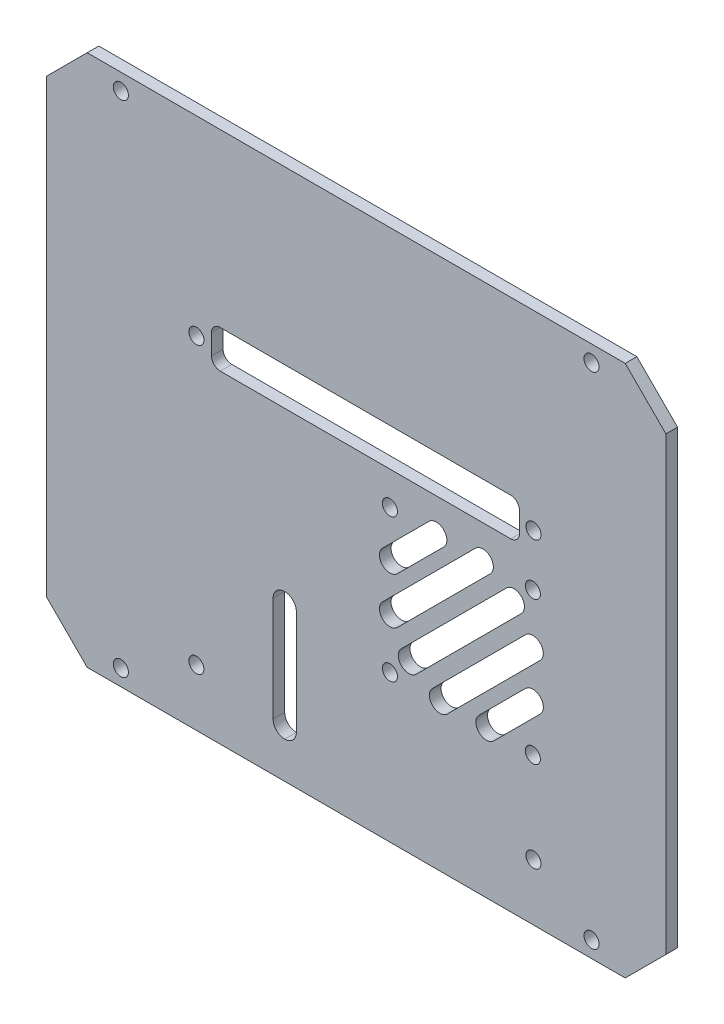
SolidWorks part; units mm, degrees
ref_plane "前视基准面" through (0, 0, 0) normal (0, 0, 1) x (1, 0, 0)
ref_plane "上视基准面" through (0, 0, 0) normal (0, 1, 0) x (1, 0, 0)
ref_plane "右视基准面" through (0, 0, 0) normal (1, 0, 0) x (0, 0, -1)
sketch "草图2" plane through (0, 0, -42.2) normal (0, 0, -1) x (-1, 0, 0)
  line L32 (-57.3467, -34.0538) -> (-50.3426, -41.058)
  line L33 (-50.3426, -41.058) -> (42.2491, -41.058)
  line L34 (42.2491, -41.058) -> (49.2533, -34.0538)
  line L35 (49.2533, -34.0538) -> (49.2533, 43.5378)
  line L36 (49.2533, 43.5378) -> (42.2491, 50.542)
  line L37 (-57.3467, 43.5378) -> (-57.3467, -34.0538)
  line L38 (-50.3426, 50.542) -> (-57.3467, 43.5378)
  line L39 (42.2491, 50.542) -> (-50.3426, 50.542)
  line L40 (-57.3467, -34.0538) -> (-50.3426, -41.058)
  line L41 (-50.3426, -41.058) -> (42.2491, -41.058)
  line L42 (42.2491, -41.058) -> (49.2533, -34.0538)
  line L43 (49.2533, -34.0538) -> (49.2533, 43.5378)
  line L44 (49.2533, 43.5378) -> (42.2491, 50.542)
  line L45 (-57.3467, 43.5378) -> (-57.3467, -34.0538)
  line L46 (-50.3426, 50.542) -> (-57.3467, 43.5378)
  line L47 (42.2491, 50.542) -> (-50.3426, 50.542)
  dimension "D1" = 0.2
extrude "凸台-拉伸1" add sketch "草图2" along normal blind 2
sketch "草图3" plane through (0, 0, -44.2) normal (0, 0, -1) x (-1, 0, 0)
  circle A0 centre (-44.5467, -38.258) radius 1.3
  circle A1 centre (36.4533, -38.258) radius 1.3
  circle A2 centre (-44.5467, 47.742) radius 1.3
  circle A3 centre (36.4533, 47.742) radius 1.3
  dimension "D1" = 2.6
extrude "切除-拉伸1" cut sketch "草图3" against normal through all
sketch "草图4" plane through (0, 0, -44.2) normal (0, 0, -1) x (-1, 0, 0)
  circle A1 centre (23.4533, -31.2932) radius 1.3
  circle A2 centre (23.4533, -31.2932) radius 1.3
  circle A3 centre (-34.5583, -31.2932) radius 1.3
  circle A4 centre (-34.5583, -31.2932) radius 1.3
  circle A5 centre (23.4533, 17.742) radius 1.3
  circle A6 centre (23.4533, 17.742) radius 1.3
  circle A7 centre (-34.5583, 17.742) radius 1.3
  circle A8 centre (-34.5583, 17.742) radius 1.3
  dimension "D1" = 0
  dimension "D2" = 0
  dimension "D3" = 0
  dimension "D4" = 0
extrude "切除-拉伸2" cut sketch "草图4" against normal up to next
sketch "草图5" plane through (0, 0, -44.2) normal (0, 0, -1) x (-1, 0, 0)
  line L0 (-50.4254, -41.258) -> (42.3319, -41.258) construction
  line L1 (-32.1467, 14.542) -> (20.8533, 14.542)
  line L2 (-32.1467, 14.542) -> (-32.1467, 21.042)
  line L3 (-32.1467, 21.042) -> (20.8533, 21.042)
  line L4 (20.8533, 14.542) -> (20.8533, 21.042)
  line L7 (-57.3467, 43.5378) -> (-57.3467, -34.0538) construction
  dimension "D1" = 53
  dimension "D2" = 6.5
  dimension "D3" = 25.2
  dimension "D4" = 55.8
extrude "切除-拉伸3" cut sketch "草图5" against normal up to next
fillet "圆角1" radius 1.5 4 edges at (32.1467, 21.042, -43.2) (32.1467, 14.542, -43.2) (-20.8533, 14.542, -43.2) (-20.8533, 21.042, -43.2)
sketch "草图7" plane through (0, 0, -44.2) normal (0, 0, -1) x (-1, 0, 0)
  line L0 (-59.0467, 44.242) -> (-59.0467, -34.758) construction
  line L1 (42.9533, 52.242) -> (-51.0467, 52.242) construction
  circle A0 centre (-34.4467, 8.842) radius 1.3
  circle A1 centre (-34.4467, -15.758) radius 1.3
  circle A2 centre (-9.8467, 8.842) radius 1.3
  circle A3 centre (-9.8467, -15.758) radius 1.3
  dimension "D1" = 24.6
  dimension "D2" = 24.6
  dimension "D3" = 24.6
  dimension "D4" = 43.4
extrude "切除-拉伸4" cut sketch "草图7" against normal up to next
sketch "草图8" plane through (0, 0, -44.2) normal (0, 0, -1) x (-1, 0, 0)
  line L0 (-34.4467, 8.842) -> (-9.8467, -15.758) construction
  line L1 (-34.4467, 8.842) -> (-9.8467, 8.842) construction
  line L2 (-34.4467, 8.842) -> (-34.4467, -15.758) construction
  line L3 (-34.4467, -15.758) -> (-9.8467, -15.758) construction
  line L4 (-9.8467, 8.842) -> (-9.8467, -15.758) construction
  line L5 (-31.194, 5.5893) -> (-13.0994, -12.5053) construction
  line L6 (-29.9212, 6.8621) -> (-11.8266, -11.2325)
  line L7 (-32.4668, 4.3165) -> (-14.3722, -13.7781)
  line L8 (-34.4467, 0.242) -> (-18.4467, -15.758) construction
  line L9 (-33.1739, 1.5148) -> (-17.1739, -14.4852)
  line L10 (-35.7195, -1.0308) -> (-19.7195, -17.0308)
  line L11 (-25.8467, 8.842) -> (-9.8467, -7.158) construction
  line L12 (-24.5739, 10.1148) -> (-8.5739, -5.8852)
  line L13 (-27.1195, 7.5692) -> (-11.1195, -8.4308)
  line L14 (-17.8467, 8.842) -> (-9.8467, 0.842) construction
  line L15 (-16.5739, 10.1148) -> (-8.5739, 2.1148)
  line L16 (-19.1195, 7.5692) -> (-11.1195, -0.4308)
  line L17 (-34.4467, -7.758) -> (-26.4467, -15.758) construction
  line L18 (-33.1739, -6.4852) -> (-25.1739, -14.4852)
  line L19 (-35.7195, -9.0308) -> (-27.7195, -17.0308)
  line L20 (42.9533, 52.242) -> (-51.0467, 52.242) construction
  line L22 (-59.0467, 44.242) -> (-59.0467, -34.758) construction
  arc A1 (-29.9212, 6.8621) -> (-32.4668, 4.3165) centre (-31.194, 5.5893) ccw
  arc A2 (-14.3722, -13.7781) -> (-11.8266, -11.2325) centre (-13.0994, -12.5053) ccw
  arc A3 (-33.1739, 1.5148) -> (-35.7195, -1.0308) centre (-34.4467, 0.242) ccw
  arc A4 (-19.7195, -17.0308) -> (-17.1739, -14.4852) centre (-18.4467, -15.758) ccw
  arc A5 (-24.5739, 10.1148) -> (-27.1195, 7.5692) centre (-25.8467, 8.842) ccw
  arc A6 (-11.1195, -8.4308) -> (-8.5739, -5.8852) centre (-9.8467, -7.158) ccw
  arc A7 (-16.5739, 10.1148) -> (-19.1195, 7.5692) centre (-17.8467, 8.842) ccw
  arc A8 (-11.1195, -0.4308) -> (-8.5739, 2.1148) centre (-9.8467, 0.842) ccw
  arc A9 (-33.1739, -6.4852) -> (-35.7195, -9.0308) centre (-34.4467, -7.758) ccw
  arc A10 (-27.7195, -17.0308) -> (-25.1739, -14.4852) centre (-26.4467, -15.758) ccw
  point P10 (-22.1467, -3.458)
  point P15 (-26.4467, -7.758)
  point P22 (-17.8467, 0.842)
  point P29 (-13.8467, 4.842)
  point P36 (-30.4467, -11.758)
  dimension "D1" = 1.8
  dimension "D2" = 1.8
  dimension "D3" = 1.8
  dimension "D4" = 1.8
  dimension "D5" = 1.8
  dimension "D6" = 8
  dimension "D7" = 8
  dimension "D8" = 8
  dimension "D9" = 8
  dimension "D10" = 4.6
  dimension "D11" = 4.6
  dimension "D12" = 43.4
  dimension "D13" = 68
  dimension "D14" = 24.6
extrude "切除-拉伸5" cut sketch "草图8" against normal up to next
sketch "草图9" plane through (0, 0, -44.2) normal (0, 0, -1) x (-1, 0, 0)
  line L0 (49.2533, -34.0538) -> (49.2533, 43.5378) construction
  line L1 (6.2533, -12.758) -> (10.2533, -12.758)
  line L2 (6.2533, -12.758) -> (6.2533, -34.758)
  line L3 (6.2533, -34.758) -> (10.2533, -34.758)
  line L4 (10.2533, -12.758) -> (10.2533, -34.758)
  line L6 (-51.0467, -42.758) -> (42.9533, -42.758) construction
  dimension "D1" = 39
  dimension "D2" = 4
  dimension "D3" = 22
  dimension "D4" = 8
extrude "切除-拉伸6" cut sketch "草图9" against normal blind 8
fillet "圆角2" radius 2 4 edges at (-6.2533, -34.758, -43.2) (-10.2533, -34.758, -43.2) (-10.2533, -12.758, -43.2) (-6.2533, -12.758, -43.2)
sketch "草图10" plane through (0, 0, -44.2) normal (0, 0, -1) x (-1, 0, 0)
  line L0 (23.4533, -31.2932) -> (23.4533, -2.7979) construction
  line L1 (36.4533, -38.258) -> (36.4533, -17.4808) construction
  line L2 (36.4533, -17.758) -> (36.4533, -29.758) construction
  line L3 (37.9533, -17.758) -> (37.9533, -29.758)
  line L4 (34.9533, -17.758) -> (34.9533, -29.758)
  line L5 (50.9533, -34.758) -> (50.9533, 44.242) construction
  line L6 (-51.0467, -42.758) -> (42.9533, -42.758) construction
  arc A0 (37.9533, -17.758) -> (34.9533, -17.758) centre (36.4533, -17.758) ccw
  arc A1 (34.9533, -29.758) -> (37.9533, -29.758) centre (36.4533, -29.758) ccw
  point P8 (36.4533, -23.758)
  dimension "D1" = 1.5
  dimension "D2" = 12
  dimension "D3" = 14.5
  dimension "D4" = 13
